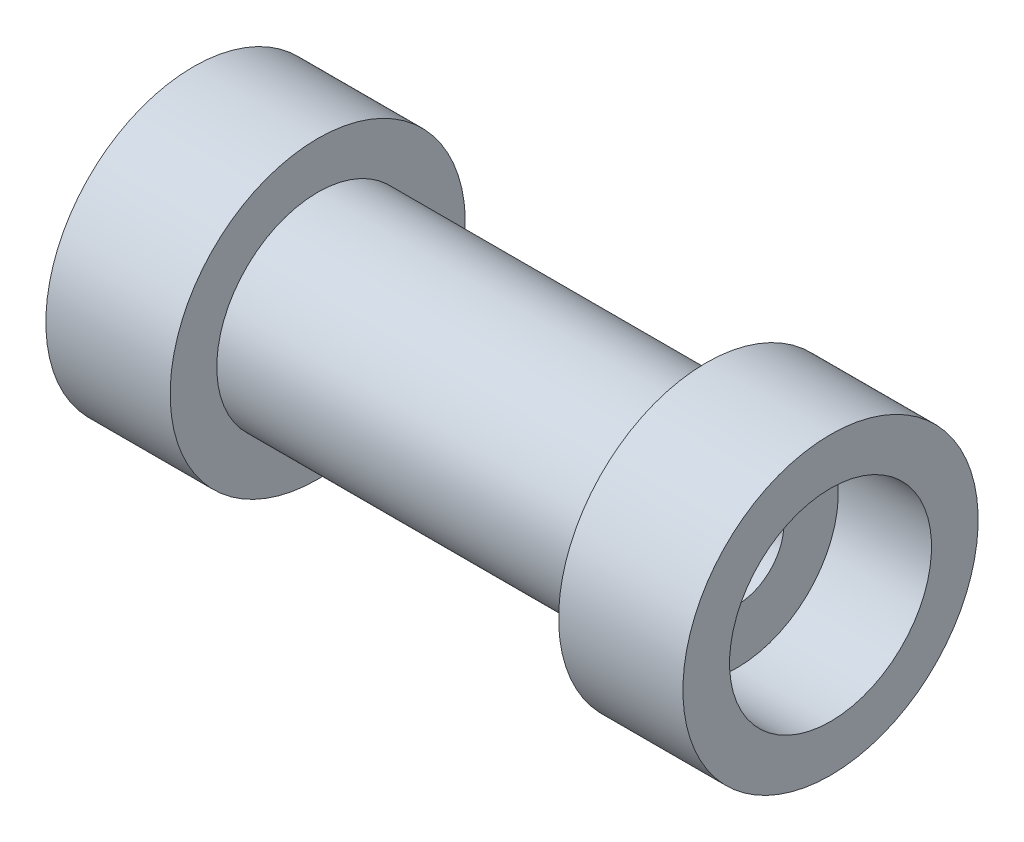
SolidWorks part; units mm, degrees
ref_plane "Front Plane" through (0, 0, 0) normal (0, 0, 1) x (1, 0, 0)
ref_plane "Top Plane" through (0, 0, 0) normal (0, 1, 0) x (1, 0, 0)
ref_plane "Right Plane" through (0, 0, 0) normal (1, 0, 0) x (0, 0, -1)
sketch "Sketch1" plane through (0, 0, 0) normal (0, 0, 1) x (1, 0, 0)
  line L0 (-41.2732, 0) -> (44.9867, 0) construction
  line L1 (0, 20.4244) -> (0, -23.7135) construction
  line L2 (-12.5, 6.5) -> (12.5, 6.5)
  line L3 (12.5, 6.5) -> (12.5, 9.5)
  line L4 (12.5, 9.5) -> (20.5, 9.5)
  line L5 (20.5, 9.5) -> (20.5, 6.5)
  line L6 (20.5, 6.5) -> (14.5, 6.5)
  line L7 (14.5, 6.5) -> (14.5, 0)
  line L8 (-20.5, 9.5) -> (-20.5, 6.5)
  line L9 (-20.5, 6.5) -> (-14.5, 6.5)
  line L10 (-12.5, 9.5) -> (-20.5, 9.5)
  line L11 (-12.5, 6.5) -> (-12.5, 9.5)
  line L12 (-14.5, 6.5) -> (-14.5, 0)
  line L13 (-14.5, 0) -> (14.5, 0)
  point P7 (0, 6.5)
  point P8 (17.5, 6.5)
  dimension "D1" = 12.5
  dimension "D2" = 6.5
  dimension "D3" = 2
  dimension "D4" = 6.5
  dimension "D5" = 3
  dimension "D6" = 6
revolve "Revolve1" add sketch "Sketch1" angle 360 about L13
sketch "Sketch2" plane through (-14.5, 0, 0) normal (-1, 0, 0) x (0, 0, 1)
  circle A0 centre (0, 0) radius 3
  dimension "D1" = 6
extrude "Cut-Extrude1" cut sketch "Sketch2" against normal through all
